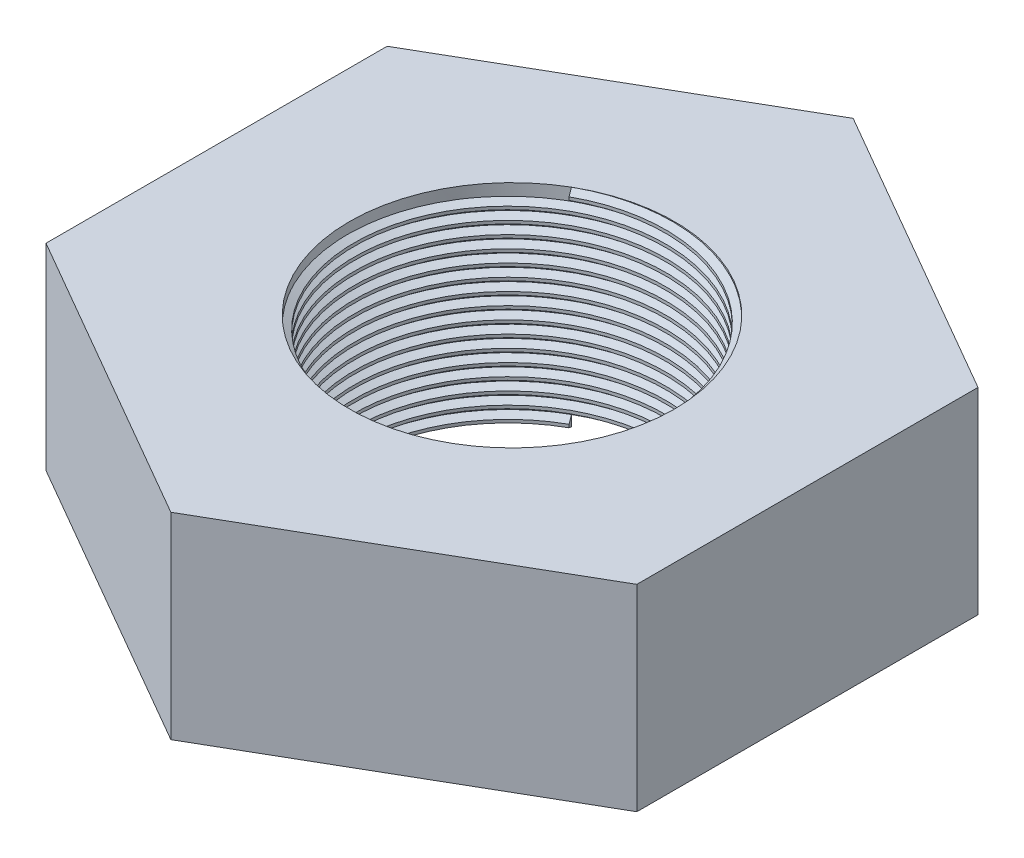
SolidWorks part; units mm, degrees
ref_plane "Front Plane" through (0, 0, 0) normal (0, 0, 1) x (1, 0, 0)
ref_plane "Top Plane" through (0, 0, 0) normal (0, 1, 0) x (1, 0, 0)
ref_plane "Right Plane" through (0, 0, 0) normal (1, 0, 0) x (0, 0, -1)
sketch "Sketch1" plane through (0, 0, 0) normal (0, 1, 0) x (1, 0, 0)
  line L0 (0, 0) -> (-6, 0) construction
  line L1 (-6, 3.4641) -> (-6, -3.4641)
  line L2 (-6, -3.4641) -> (0, -6.9282)
  line L3 (0, -6.9282) -> (6, -3.4641)
  line L4 (6, -3.4641) -> (6, 3.4641)
  line L5 (6, 3.4641) -> (0, 6.9282)
  line L6 (0, 6.9282) -> (-6, 3.4641)
  circle A0 centre (0, 0) radius 6 construction
  dimension "D1" = 12
  dimension "D2" = 90
extrude "Boss-Extrude1" add sketch "Sketch1" along normal blind 8
hole_wizard "CBORE for M6 Hex Head Bolt1" positions "Sketch4" profile "Sketch5" counterbore size "M6" standard "ISO" end condition through all
sketch "Sketch4" plane through (0, 0, 0) normal (0, -1, 0) x (-1, 0, 0)
  point P0 (0, 0)
  dimension "D1" = 0
sketch "Sketch5" plane through (0, 0, 0) normal (1, 0, 0) x (0, 0, -1)
  line L0 (0, 0) -> (0, 8)
  line L1 (0, 8) -> (3.3, 8)
  line L3 (3.3, 8) -> (3.3, 4)
  line L4 (3.3, 4) -> (7.2735, 4)
  line L5 (7.2735, 4) -> (7.2735, 0)
  line L7 (7.2735, 0) -> (0, 0)
  line L11 (0, -6.35) -> (0, 107.95) construction
  dimension "Thru Hole Dia." = 6.6
  dimension "Thru Hole Depth" = 8
  dimension "C'Bore Dia." = 14.547
  dimension "C'Bore Depth" = 4
sketch "Sketch8" plane through (0, 4, 0) normal (0, -1, 0) x (1, 0, 0)
  circle A0 centre (0, 0) radius 3.3
thread "Thread1" pitch 0.25 method extrude profile "Thread Profile1" start angle 60, offset 0, length 4, pitch 0.25, diameter 6.6
ref_plane "Plane2" through (-1.65, 8, -2.8579) normal (-0.866, 0, 0.5) x (-0.5, 0, -0.866)
sketch "Thread Profile1" plane through (-1.65, 8, -2.8579) normal (-0.866, 0, 0.5) x (-0.5, 0, -0.866)
  line L0 (0, 0) -> (0, 0.25) construction
  line L11 (0, 0) -> (0, 0.2187)
  line L12 (0, 0.2187) -> (-0.1353, 0.1406)
  line L13 (-0.1353, 0.1406) -> (-0.1353, 0.0781)
  line L15 (-0.1353, 0.0781) -> (0, 0)
  line L17 (-0.1353, 0.1094) -> (0, 0.1094) construction
  point P2 (0, 0)
  dimension "Pitch" = 0.25
  dimension "Profile_Angle" = 60
  dimension "Profile_Land" = 0.0625
  dimension "Profile_Height" = 0.1353
